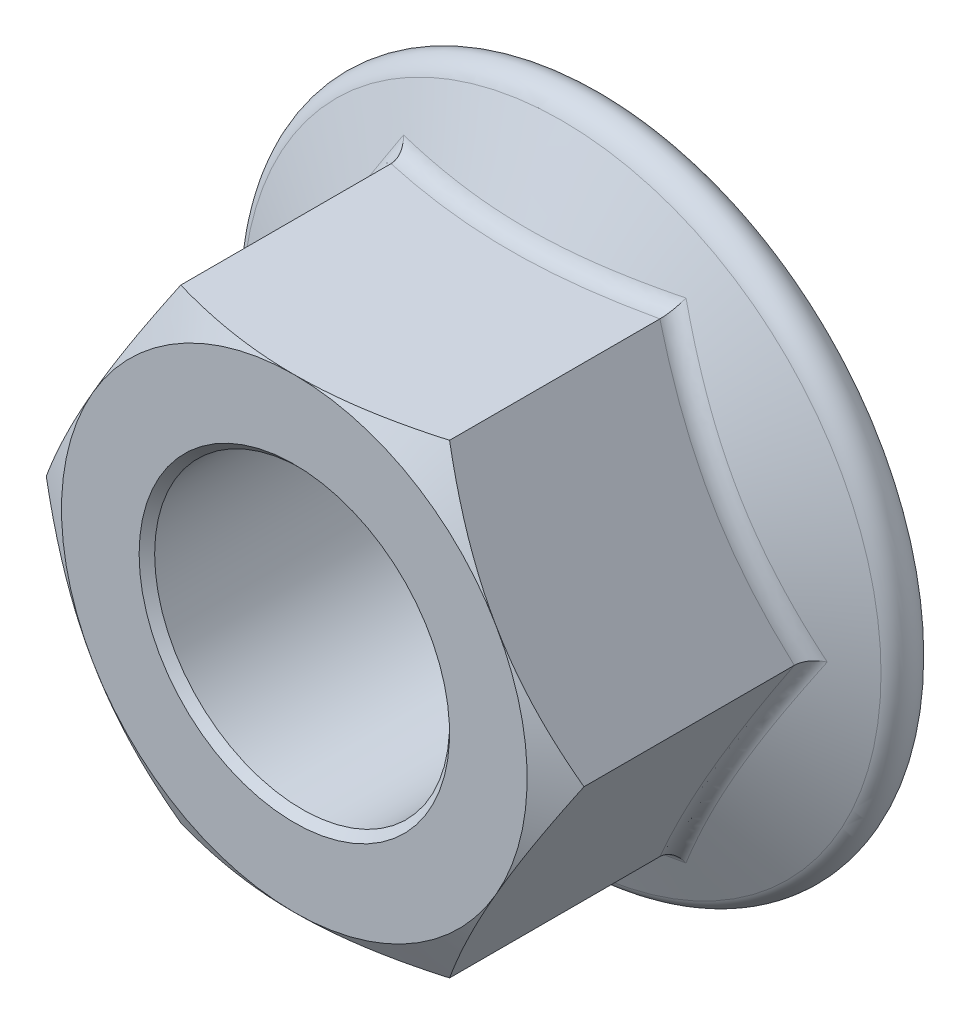
SolidWorks part; units mm, degrees
ref_plane "Front" through (0, 0, 0) normal (0, 0, 1) x (1, 0, 0)
ref_plane "Top" through (0, 0, 0) normal (0, 1, 0) x (1, 0, 0)
ref_plane "Right" through (0, 0, 0) normal (1, 0, 0) x (0, 0, -1)
other "Configuration Table"
sketch "Sketch1" plane through (0, 0, 0) normal (0, 0, 1) x (1, 0, 0)
  line L1 (8.6603, -15) -> (17.3205, 0)
  line L2 (17.3205, 0) -> (8.6603, 15)
  line L3 (8.6603, 15) -> (-8.6603, 15)
  line L4 (-8.6603, 15) -> (-17.3205, 0)
  line L5 (-17.3205, 0) -> (-8.6603, -15)
  line L6 (-8.6603, -15) -> (8.6603, -15)
  circle A0 centre (0, 0) radius 15 construction
  circle A1 centre (0, 0) radius 9.5
extrude "BaseNut" add sketch "Sketch1" against normal blind 20
cosmetic thread "ThreadCosmetic1" [suppressed] parameters "D2"=20
sketch "Sketch3" plane through (0.6779, 0, -16.6426) normal (0, 1, 0) x (0, 0, -1)
  line L0 (4.0352, 0.6779) -> (-19.0613, 0.6779) construction
  line L2 (-16.6426, 15.6779) -> (-15.3029, 17.9984)
  line L4 (-15.3029, 17.9984) -> (-16.6426, 17.9984)
  line L5 (-16.6426, 17.9984) -> (-16.6426, 15.6779)
  line L6 (-6.6426, 17.9984) -> (-6.6426, 14.238) construction
  line L8 (3.3574, 17.9984) -> (3.3574, 15.6779)
  line L9 (2.0176, 17.9984) -> (3.3574, 17.9984)
  line L10 (3.3574, 15.6779) -> (2.0176, 17.9984)
  line L11 (3.3574, 17.9984) -> (-16.6426, 17.9984) construction
  dimension "D1" = 30
revolve "Double-Chamfer" cut sketch "Sketch3" angle 360 about L0
sketch "Sketch4" plane through (4.6827, 0, -16.7173) normal (0, 1, 0) x (0, 0, -1)
  line L0 (-21.7744, 4.6827) -> (9.7398, 4.6827) construction
  line L2 (-4.6401, 30.5008) -> (-4.6401, 8.9315) construction
  line L3 (0.5185, 25.2455) -> (-4.6401, 14.1827)
  line L4 (3.2827, 14.1827) -> (-16.7173, 14.1827) construction
  line L5 (3.2827, 14.1827) -> (3.2827, 24.6327)
  line L11 (-4.6401, 14.1827) -> (3.2827, 14.1827)
  arc A0 (3.2827, 24.6327) -> (0.5185, 25.2455) centre (1.8327, 24.6327) ccw
revolve "Flange" add sketch "Sketch4" angle 360 about L0
fillet "FlangeFillet" radius 1.2 6 edges at (-10.9757, -10.9896, -14.8899) (-15.0051, 4.0104, -14.8899) (10.9757, 10.9896, -14.8899) (15.0051, -4.0104, -14.8899)
sketch "Sketch5" plane through (-5.1971, 0, -15.1971) normal (0, 1, 0) x (0, 0, -1)
  line L0 (3.5984, -5.1971) -> (-23.9926, -5.1971) construction
  line L1 (4.8029, 4.3029) -> (-15.1971, 4.3029) construction
  line L2 (-15.1971, 4.8029) -> (-15.1971, 4.3029)
  line L4 (-15.1971, 4.3029) -> (-14.6971, 4.3029)
  line L6 (-14.6971, 4.3029) -> (-15.1971, 4.8029)
  line L7 (-5.1971, 4.3029) -> (-5.1971, 0.9419) construction
  line L8 (4.3029, 4.3029) -> (4.8029, 4.8029)
  line L9 (4.8029, 4.3029) -> (4.3029, 4.3029)
  line L10 (4.8029, 4.8029) -> (4.8029, 4.3029)
  dimension "da" = 20
  dimension "D2" = 45
revolve "Hole" cut sketch "Sketch5" angle 360 about L0
sketch "Sketch6" plane through (0, 0, 0) normal (0, 1, 0) x (1, 0, 0)
  line L0 (-9.933, 0.5) -> (-9.5, 0.25)
  line L1 (-9.5, 0.25) -> (-9, 0.25)
  line L2 (-9, 0.25) -> (-9, 0.75)
  line L3 (-9, 0.75) -> (-9.5, 0.75)
  line L4 (-9.5, 0.75) -> (-9.933, 0.5)
  line L5 (0, 7.348) -> (0, 34.1252) construction
revolve "Cut-Revolve10" [suppressed] cut sketch "Sketch6" angle 360 about L5
pattern_linear "LPattern10" [suppressed] count 33 spacing 0.6 along (0, 0, -1) of bodies 105
equation "\"m1@Sketch4\" = \"m@BaseNut\""
equation "\"sq@Sketch3\" = \"s@Sketch1\""
equation "\"D2@Sketch6\"=\"D1@Sketch1\""
equation "\"D1@Sketch6\"= (\"D2@ThreadCosmetic1\"  - \"D2@Sketch6\" )  / 2"
equation "\"D3@LPattern10\"=\"D1@Sketch6\" * 1.2 "
equation "\"D1@LPattern10\"=\"m@BaseNut\"  / \"D3@LPattern10\""
